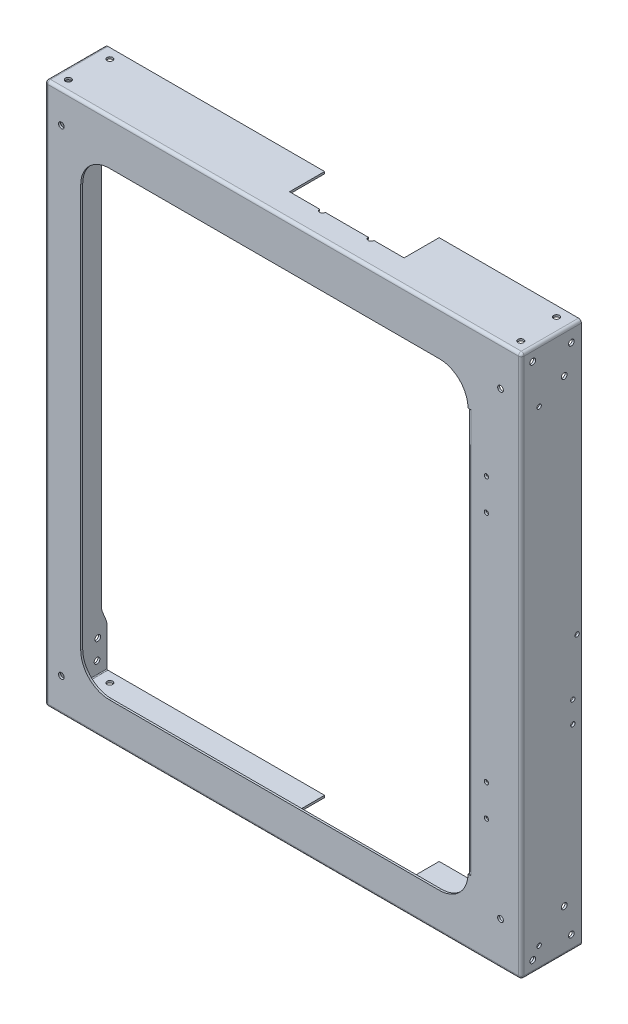
SolidWorks part; units mm, degrees
ref_plane "Спереди" through (0, 0, 0) normal (0, 0, 1) x (1, 0, 0)
ref_plane "Сверху" through (0, 0, 0) normal (0, 1, 0) x (1, 0, 0)
ref_plane "Справа" through (0, 0, 0) normal (1, 0, 0) x (0, 0, -1)
ref_plane "Плоскость1"
sketch "Эскиз1" plane through (0, 0, 0) normal (0, 0, 1) x (1, 0, 0)
  line L0 (0, 0) -> (332.7, 0)
  line L1 (332.7, 0) -> (332.7, -378.7)
  line L2 (332.7, -378.7) -> (0, -378.7)
  line L3 (0, -378.7) -> (0, 0)
  line L4 (295.5, -31.2) -> (25, -31.2)
  line L5 (25, -31.2) -> (25, -352.7)
  line L6 (25, -352.7) -> (295.5, -352.7)
  line L7 (295.5, -352.7) -> (295.5, -31.2)
  dimension "D1" = 378.7
  dimension "D2" = 332.7
  dimension "D3" = 321.5
  dimension "D4" = 270.5
  dimension "D5" = 26
  dimension "D6" = 31.2
  dimension "D7" = 37.2
  dimension "D8" = 25
extrude "Выдавливание1" add sketch "Эскиз1" against normal blind 1.4 contours L3 L2 L1 L0 L7 L6 L5 L4
sketch "Эскиз2" plane through (0, 0, 0) normal (0, 0, 1) x (1, 0, 0)
  line L0 (0, 0) -> (332.7, 0)
  line L1 (332.7, 0) -> (332.7, -378.7)
  line L2 (332.7, -378.7) -> (0, -378.7)
  line L3 (0, -378.7) -> (0, 0)
  line L4 (331.3, -1.4) -> (1.4, -1.4)
  line L5 (1.4, -1.4) -> (1.4, -377.3)
  line L6 (1.4, -377.3) -> (331.3, -377.3)
  line L7 (331.3, -377.3) -> (331.3, -1.4)
  line L8 (25, -352.7) -> (295.5, -352.7) construction
  line L9 (295.5, -31.2) -> (25, -31.2) construction
  line L10 (295.5, -352.7) -> (295.5, -31.2) construction
  line L11 (25, -31.2) -> (25, -352.7) construction
  line M5 (0, 0) -> (0, -378.7)
  line M6 (0, -378.7) -> (332.7, -378.7)
  line M7 (332.7, -378.7) -> (332.7, 0)
  line M8 (332.7, 0) -> (0, 0)
  dimension "D1" = 378.7
  dimension "D2" = 332.7
  dimension "D3" = 321.5
  dimension "D4" = 270.5
  dimension "D5" = 26
  dimension "D6" = 31.2
  dimension "D7" = 37.2
  dimension "D8" = 25
extrude "Выдавливание2" add sketch "Эскиз2" against normal blind 42 contours L7 L6 L5 L4 M8 M5 M6 M7
fillet "Сопряжение1" radius 2 8 edges at (0, -189.35, 0) (332.7, 0, -21) (332.7, -189.35, 0) (332.7, -378.7, -21) (0, -378.7, -21) (166.35, -378.7, 0) (166.35, 0, 0) (0, 0, -21)
fillet "Сопряжение2" radius 0.6 8 edges at (166.35, -377.3, -1.4) (1.4, -377.3, -21.7) (331.3, -377.3, -21.7) (331.3, -189.35, -1.4) (331.3, -1.4, -21.7) (166.35, -1.4, -1.4) (1.4, -1.4, -21.7) (1.4, -189.35, -1.4)
sketch "Эскиз3" plane through (0, 0, 0) normal (-1, 0, 0) x (0, 0, 1)
  line L0 (-42, -30) -> (-42, -348.7)
  line L1 (-42, -348.7) -> (-38, -338.7)
  line L2 (-38, -338.7) -> (-38, -40)
  line L3 (-38, -40) -> (-42, -30)
extrude "Выдавливание3" cut sketch "Эскиз3" against normal blind 2
fillet "Сопряжение3" radius 10 4 edges at (0.7, -348.7, -42) (0.7, -338.7, -38) (0.7, -40, -38) (0.7, -30, -42)
sketch "Эскиз4" plane through (0, -378.7, 0) normal (0, -1, 0) x (1, 0, 0)
  line L0 (153.35, -42) -> (233.35, -42)
  line L1 (233.35, -42) -> (233.35, -17.5)
  line L2 (233.35, -17.5) -> (212.35, -17.5)
  line L3 (153.35, -17.5) -> (153.35, -42)
  line L4 (332.7, -42) -> (332.7, 0) construction
  line L5 (2, -42) -> (330.7, -42) construction
  line L6 (174.35, -17.5) -> (153.35, -17.5)
  line L7 (208.35, -17.5) -> (178.35, -17.5)
  arc A0 (178.35, -17.5) -> (174.35, -17.5) centre (176.35, -17.5) ccw
  arc A1 (212.35, -17.5) -> (208.35, -17.5) centre (210.35, -17.5) ccw
  dimension "D2" = 4
  dimension "D3" = 4
  dimension "D1" = 80
  dimension "D4" = 34
  dimension "D5" = 24.5
  dimension "D6" = 23
  dimension "D7" = 99.35
extrude "Выдавливание4" cut sketch "Эскиз4" against normal blind 500
fillet "Сопряжение5" radius 20 4 edges at (25, -31.2, -0.7) (295.5, -31.2, -0.7) (295.5, -352.7, -0.7) (25, -352.7, -0.7)
sketch "Эскиз5" plane through (0, 0, 0) normal (-1, 0, 0) x (0, 0, 1)
  circle A0 centre (-8, -8.35) radius 2
  circle A1 centre (-35, -10.35) radius 2
  circle A2 centre (-8, -370.35) radius 2
  circle A3 centre (-35, -368.35) radius 2
extrude "Выдавливание5" cut sketch "Эскиз5" against normal blind 500
sketch "Эскиз6" plane through (0, -378.7, 0) normal (0, -1, 0) x (1, 0, 0)
  circle A0 centre (8.35, -8) radius 2
  circle A1 centre (10.35, -35) radius 2
  circle A2 centre (324.35, -8) radius 2
  circle A3 centre (322.35, -35) radius 2
extrude "Выдавливание6" cut sketch "Эскиз6" against normal blind 500
ref_plane "Плоскость2"
sketch "Эскиз7" plane through (0, 0, -1.4) normal (0, 0, -1) x (-1, 0, 0)
  line L0 (-295.5, -332.7) -> (-295.5, -51.2)
  line L1 (-295.5, -51.2) -> (-296.9, -51.2)
  line L2 (-296.9, -51.2) -> (-296.9, -332.7)
  line L3 (-296.9, -332.7) -> (-295.5, -332.7)
  dimension "D1" = 1.4
extrude "Выдавливание7" add sketch "Эскиз7" along normal blind 10.6
fillet "Сопряжение6" radius 4 2 edges at (296.2, -332.7, -12) (296.2, -51.2, -12)
ref_plane "Плоскость3"
sketch "Эскиз8" plane through (0, 0, 0) normal (0, 0, 1) x (1, 0, 0)
  line L0 (295.4999, -51) -> (295.356, -51)
  line L1 (295.356, -51) -> (295.356, -51.2)
  line L2 (295.356, -51.2) -> (295.4999, -51.2)
  line L3 (295.5, -51.1999) -> (295.5, -51.0001)
  line L4 (295.5001, -51.2) -> (297.5, -51.2)
  line L5 (297.5, -51.2) -> (297.5, -51)
  line L6 (297.5, -51) -> (295.5001, -51)
  line L7 (295.5, -51) -> (295.5, -51.2)
  line L8 (295.5, -332.7) -> (291.4104, -332.7)
  line L9 (291.4104, -332.7) -> (291.4104, -332.9)
  line L10 (291.4104, -332.9) -> (297.5, -332.9)
  line L11 (297.5, -332.9) -> (297.5, -332.7)
  line L12 (297.5, -332.7) -> (295.5, -332.7)
  arc A0 (295.4999, -51.2) -> (295.5, -51.1999) centre (295.4999, -51.1999) ccw
  arc A1 (295.4999, -51) -> (295.5, -51.0001) centre (295.4999, -51.0001) cw
  arc A2 (295.5001, -51) -> (295.5, -51.0001) centre (295.5001, -51.0001) ccw
  arc A3 (295.5001, -51.2) -> (295.5, -51.1999) centre (295.5001, -51.1999) cw
  dimension "D3" = 0.0001
  dimension "D4" = 0.0001
  dimension "D1" = 0.0001
  dimension "D5" = 0.0001
  dimension "D2" = 0.2
extrude "Выдавливание8" cut sketch "Эскиз8" against normal blind 10.6 contours A1 L0 L1 L2 A0 L3 | A3 L4 L5 L6 A2 L3 | L11 L12 L8 L9 L10
fillet "Сопряжение7" radius 2 1 edges at (295.5, -191.95, 0)
sketch "Эскиз9" plane through (0, 0, 0) normal (-1, 0, 0) x (0, 0, 1)
  circle A0 centre (-12.5, -37.8) radius 1.5
  circle A1 centre (-12.5, -363.8) radius 1.5
  dimension "D1" = 3
  dimension "D2" = 3
  dimension "D3" = 326
extrude "Выдавливание9" cut sketch "Эскиз9" against normal blind 600
ref_plane "Плоскость4"
sketch "Эскиз11" plane through (0, 0, 0) normal (0, 0, 1) x (1, 0, 0)
  circle A0 centre (308.35, -107.85) radius 1.5
  circle A1 centre (308.35, -85.85) radius 1.5
  circle A2 centre (308.35, -270.85) radius 1.5
  circle A3 centre (308.35, -292.85) radius 1.5
extrude "Выдавливание11" cut sketch "Эскиз11" against normal blind 5 contours A0 | A1 | A2 | A3
sketch "Эскиз12" plane through (0, 0, 0) normal (-1, 0, 0) x (0, 0, 1)
  line L0 (0, -352.7) -> (0, -332.7) construction
  circle A0 centre (-35.5, -22) radius 2
  circle A1 centre (-35.5, -355) radius 2
  dimension "D1" = 4
  dimension "D2" = 4
  dimension "D3" = 20
  dimension "D4" = 333
extrude "Выдавливание12" cut sketch "Эскиз12" against normal blind 5
ref_plane "Плоскость5"
sketch "Эскиз13" plane through (0, 0, 0) normal (0, 0, 1) x (1, 0, 0)
  line L1 (2, 0) -> (330.7, 0) construction
  line L2 (2, -376.7) -> (330.7, -376.7) construction
  line L3 (0, -376.7) -> (0, -2) construction
  line L4 (330.7, -376.7) -> (330.7, -2) construction
  circle A0 centre (11.5, -22) radius 2
  circle A1 centre (11.5, -355) radius 2
  circle A2 centre (318.2, -28) radius 2
  circle A3 centre (318.2, -348.7) radius 2
  dimension "D1" = 4
  dimension "D2" = 4
  dimension "D8" = 4
  dimension "D9" = 4
  dimension "D4" = 348.7
  dimension "D5" = 333
  dimension "D7" = 318.2
  dimension "D10" = 12.5
  dimension "D11" = 348.7
  dimension "D12" = 11.5
  dimension "D13" = 11.5
  dimension "D14" = 22
extrude "Выдавливание13" cut sketch "Эскиз13" against normal blind 5 contours A0 | A1 | A2 | A3
sketch "Эскиз14" plane through (332.7, 0, 0) normal (1, 0, 0) x (0, 0, -1)
  circle A0 centre (30, -28) radius 2
  circle A1 centre (30, -348.7) radius 2
  dimension "D1" = 4
  dimension "D2" = 4
extrude "Выдавливание14" cut sketch "Эскиз14" against normal blind 5
sketch "Эскиз15" plane through (1.4, 0, 0) normal (1, 0, 0) x (0, 0, -1)
  circle A0 centre (27.0596, -45.7086) radius 1.5
  circle A1 centre (27.0596, -45.7086) radius 1
  dimension "D1" = 2
extrude "Выдавливание15" add sketch "Эскиз15" along normal blind 12
sketch "Эскиз16" plane through (332.7, 0, 0) normal (1, 0, 0) x (0, 0, -1)
  circle A0 centre (36, -241.7) radius 1.5
  circle A1 centre (36, -226.7) radius 1.5
  dimension "D1" = 3
  dimension "D2" = 3
  dimension "D3" = 15
extrude "Выдавливание16" cut sketch "Эскиз16" against normal blind 12
sketch "Эскиз17" plane through (332.7, 0, 0) normal (1, 0, 0) x (0, 0, -1)
  circle A0 centre (39, -188.85) radius 1.5
  dimension "D1" = 3
extrude "Выдавливание17" cut sketch "Эскиз17" against normal blind 10
